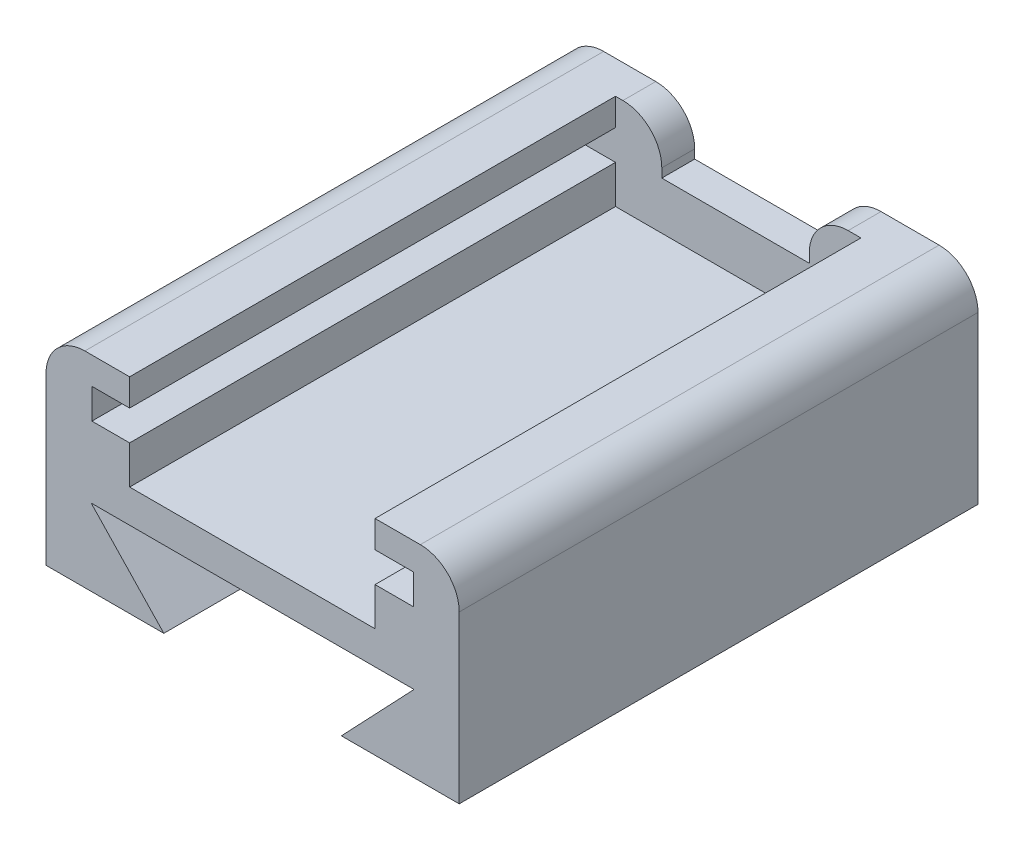
SolidWorks part; units mm, degrees
ref_plane "Front Plane" through (0, 0, 0) normal (0, 0, 1) x (1, 0, 0)
ref_plane "Top Plane" through (0, 0, 0) normal (0, 1, 0) x (1, 0, 0)
ref_plane "Right Plane" through (0, 0, 0) normal (1, 0, 0) x (0, 0, -1)
sketch "Sketch1" plane through (0, 0, 0) normal (0, 0, 1) x (1, 0, 0)
  line L1 (-61.6305, -18.2453) -> (-34.6306, -18.2453)
  line L2 (-61.6305, -18.2453) -> (-61.6305, -31.6453)
  line L3 (-61.6305, -31.6453) -> (-34.6306, -31.6453)
  line L4 (-34.6306, -18.2453) -> (-34.6306, -31.6453)
extrude "Boss-Extrude2" add sketch "Sketch1" along normal blind 33.9 contours L1 L4 L3 L2
sketch "Sketch5" plane through (0, 0, 33.9) normal (0, 0, 1) x (1, 0, 0)
  line L0 (-48.1305, -18.2453) -> (-48.1305, -31.6453) construction
  line L1 (-61.6305, -18.2453) -> (-34.6306, -18.2453) construction
  line L2 (-61.6305, -31.6453) -> (-34.6306, -31.6453) construction
  line L3 (-48.1305, -31.6453) -> (-48.1305, -24.9453) construction
  line L4 (-48.1305, -24.9453) -> (-61.6305, -24.9453) construction
  line L5 (-61.6305, -24.9453) -> (-34.6306, -24.9453) construction
  line L6 (-48.1305, -18.2453) -> (-56.1665, -18.2453)
  line L7 (-48.1305, -18.2453) -> (-40.1305, -18.2453)
  line L8 (-40.1305, -18.2453) -> (-40.1305, -20.0167)
  line L9 (-56.1665, -19.7453) -> (-56.1665, -18.2453)
  line L10 (-40.1305, -20.0167) -> (-40.1305, -21.9858)
  line L11 (-40.1305, -21.9858) -> (-40.1305, -24.4858)
  line L12 (-32.1305, -20.958) -> (-48.1305, -20.958)
  line L13 (-48.1305, -20.958) -> (-56.1665, -20.958)
  line L14 (-56.1665, -19.7453) -> (-56.1665, -24.4858)
  line L15 (-48.1305, -20.958) -> (-58.6305, -20.958)
  line L16 (-48.1305, -20.958) -> (-37.6305, -20.958)
  line L17 (-37.6305, -20.958) -> (-37.6305, -20.0167)
  line L18 (-37.6305, -20.0167) -> (-37.6305, -20.958)
  line L19 (-37.6305, -21.9858) -> (-37.6305, -20.958)
  line L20 (-37.6305, -21.9858) -> (-40.1305, -21.9858)
  line L21 (-37.6305, -20.0167) -> (-40.1305, -20.0167)
  line L22 (-58.6305, -20.958) -> (-58.6305, -20.0167)
  line L23 (-58.6305, -20.0167) -> (-58.6305, -20.958)
  line L24 (-58.6305, -21.9858) -> (-58.6305, -20.958)
  line L25 (-58.6305, -21.9858) -> (-56.1665, -21.9858)
  line L26 (-40.1305, -20.0167) -> (-58.6305, -20.0167)
  line L27 (-56.1665, -21.9858) -> (-40.1305, -21.9858)
  line L28 (-56.1665, -21.9858) -> (-56.1665, -24.4858)
  line L29 (-56.1665, -24.4858) -> (-40.1305, -24.4858)
  line L30 (-48.1305, -31.6453) -> (-42.3305, -31.6453)
  line L31 (-48.1305, -31.6453) -> (-53.9305, -31.6453)
  line L32 (-48.1305, -31.6453) -> (-48.1305, -26.6453)
  line L33 (-48.1305, -26.6453) -> (-37.5805, -26.6453)
  line L34 (-48.1305, -26.6453) -> (-58.6805, -26.6453)
  line L35 (-53.9305, -31.6453) -> (-58.6805, -26.6453)
  line L36 (-42.3305, -31.6453) -> (-37.5805, -26.6453)
  line L38 (-58.6305, -20.0167) -> (-37.6305, -20.0167)
  line L39 (-58.6305, -20.0167) -> (-58.6305, -21.9858)
  line L40 (-58.6305, -21.9858) -> (-37.6305, -21.9858)
  line L41 (-37.6305, -20.0167) -> (-37.6305, -21.9858)
  line L42 (-58.6305, -20.0167) -> (-37.6305, -20.0167)
  line L43 (-58.6305, -20.0167) -> (-58.6305, -21.9858)
  line L44 (-58.6305, -21.9858) -> (-37.6305, -21.9858)
  line L45 (-37.6305, -20.0167) -> (-37.6305, -21.9858)
  line L46 (-58.6305, -20.0167) -> (-37.6305, -20.0167)
  line L47 (-58.6305, -20.0167) -> (-58.6305, -21.9858)
  line L48 (-58.6305, -21.9858) -> (-37.6305, -21.9858)
  line L49 (-37.6305, -20.0167) -> (-37.6305, -21.9858)
  line L50 (-40.1305, -24.4858) -> (-56.1665, -24.4858)
  line L51 (-40.1305, -24.4858) -> (-40.1305, -18.2453)
  line L52 (-40.1305, -18.2453) -> (-56.1665, -18.2453)
  line L53 (-56.1665, -24.4858) -> (-56.1665, -18.2453)
  line L54 (-58.6305, -20.0167) -> (-37.6305, -20.0167)
  line L55 (-58.6305, -20.0167) -> (-58.6305, -21.9858)
  line L56 (-58.6305, -21.9858) -> (-37.6305, -21.9858)
  line L57 (-37.6305, -20.0167) -> (-37.6305, -21.9858)
  point P18 (-40.1305, -20.958)
  line M2 (-61.6305, -31.6453) -> (-34.6306, -31.6453)
  line M4 (-34.6306, -18.2453) -> (-61.6305, -18.2453)
fillet "Fillet2" radius 2.54 1 edges at (-61.6305, -18.2453, 16.95)
fillet "Fillet6" radius 2.54 1 edges at (-34.6306, -18.2453, 16.95)
extrude "Cut-Extrude3" cut sketch "Sketch5" against normal blind 31.75 contours L10 L26 L14 L13 L12 | L14 L26 L22 L15 | L24 L25 L14 L15 | L14 L27 L10 L12 L13 | L14 L29 L11 L27 | L20 L19 L12 L10 | L17 L21 L10 L12 | L26 L8 L9 L14 M4 region at (-48.1485, -19.131, 33.9) region at (-38.8805, -20.4873, 33.9) region at (-48.1485, -20.4873, 33.9) region at (-57.3985, -20.4873, 33.9) region at (-38.8805, -21.4719, 33.9) region at (-48.1485, -21.4719, 33.9) region at (-57.3985, -21.4719, 33.9) region at (-48.1485, -23.2358, 33.9)
extrude "Cut-Extrude4" cut sketch "Sketch5<10>" against normal blind 21.1 contours L35 L32 L34 M2 | L36 L33 L32 M2 region at (-43.928, -28.9032, 33.9) region at (-52.333, -28.9032, 33.9)
sketch "Sketch5<10>" plane through (0, 0, 33.9) normal (0, 0, 1) x (1, 0, 0) same geometry as "Sketch5"
sketch "Sketch13" plane through (0, 0, 2.15) normal (0, 0, 1) x (1, 0, 0)
  line L0 (-48.3323, -18.2453) -> (-48.3323, -24.4858) construction
  line L1 (-40.1305, -18.2453) -> (-56.1665, -18.2453) construction
  line L2 (-56.1665, -24.4858) -> (-40.1305, -24.4858) construction
  line L5 (-48.3323, -21.3655) -> (-48.3323, -18.2453)
  line L7 (-53.1434, -21.3655) -> (-53.1434, -18.2453)
  line L8 (-43.5063, -21.3655) -> (-43.5063, -18.2453)
  line L15 (-43.5063, -21.3655) -> (-53.1434, -21.3655)
  line L17 (-43.5063, -18.2453) -> (-53.1434, -18.2453)
  line M10 (-40.1305, -18.2453) -> (-56.1665, -18.2453)
extrude "Cut-Extrude5" cut sketch "Sketch13" against normal blind 21.1 contours L15 L5 L7 M10 | L15 L8 L5 M10 region at (-50.7378, -19.8054, 2.15) region at (-45.9193, -19.8054, 2.15)
fillet "Fillet7" radius 2.54 1 edges at (-53.1434, -18.2453, 1.075)
fillet "Fillet8" radius 2.54 1 edges at (-43.5063, -18.2453, 1.075)
sketch "Sketch14" plane through (-61.6305, 0, 0) normal (-1, 0, 0) x (0, 0, 1)
  text T0 "v1.0" font "Tw Cen MT Condensed" height 5.08
extrude "Cut-Extrude6" cut sketch "Sketch14" against normal blind 0.5
